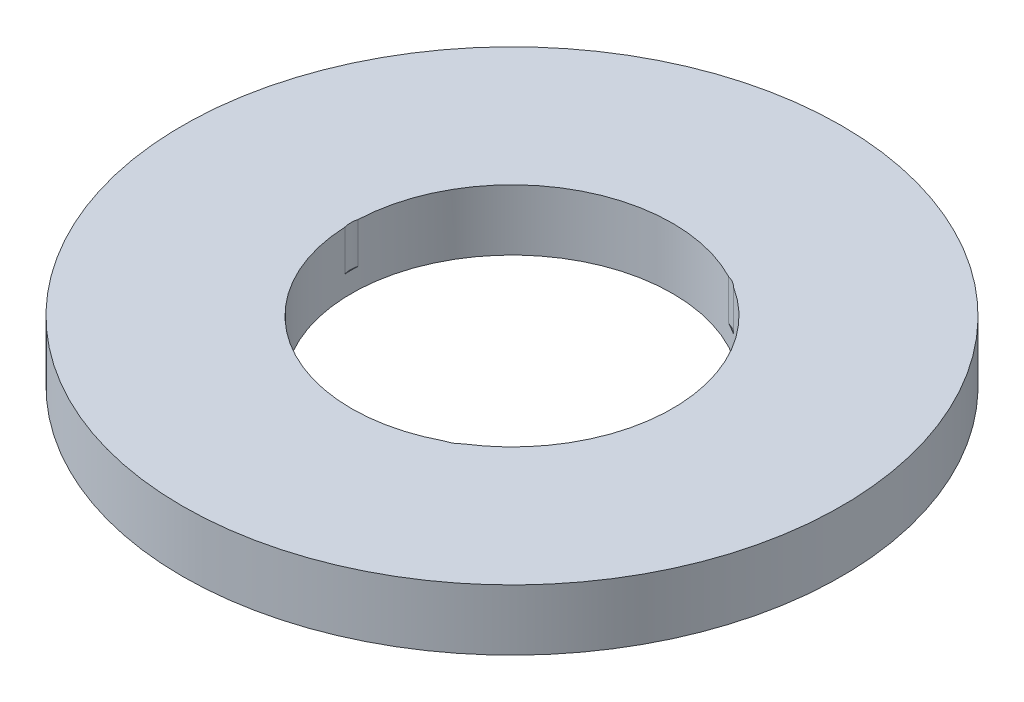
SolidWorks part; units mm, degrees
ref_plane "Front Plane" through (0, 0, 0) normal (0, 0, 1) x (1, 0, 0)
ref_plane "Top Plane" through (0, 0, 0) normal (0, 1, 0) x (1, 0, 0)
ref_plane "Right Plane" through (0, 0, 0) normal (1, 0, 0) x (0, 0, -1)
sketch "Sketch1" plane through (0, 0, 0) normal (0, 1, 0) x (1, 0, 0)
  circle A0 centre (0, 0) radius 97.5
  dimension "FLANGE_OD" = 195
extrude "Boss-Extrude1" add sketch "Sketch1" along normal blind 18
sketch "Sketch2" plane through (0, 0, 0) normal (0, 1, 0) x (1, 0, 0)
  circle A0 centre (0, 0) radius 47.5
  dimension "BORE_D" = 95
extrude "Cut-Extrude1" cut sketch "Sketch2" along normal through all
sketch "Sketch3" plane through (0, 18, 0) normal (0, 1, 0) x (1, 0, 0)
  circle A0 centre (0, 0) radius 40.2768 construction
  circle A1 centre (-40.2768, 0) radius 7.445
  dimension "BOLT_D" = 14.89
  dimension "BOLT_PCD" = 80.5537
extrude "Cut-Extrude2" cut sketch "Sketch3" against normal blind 12.0066
pattern_circular "CirPattern1" count 3 over 360 about axis through (0, 0, 0) along (0, 1, 0) of "Cut-Extrude2"
